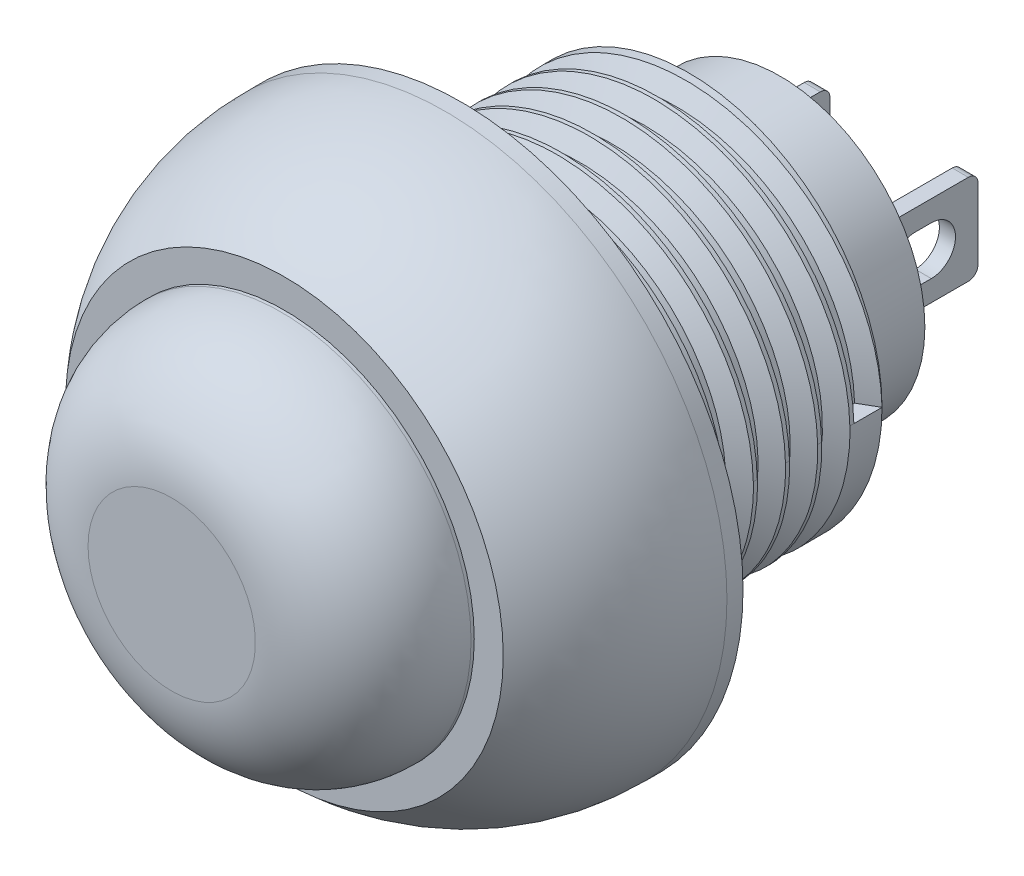
SolidWorks part; units mm, degrees
ref_plane "Front Plane" through (0, 0, 0) normal (0, 0, 1) x (1, 0, 0)
ref_plane "Top Plane" through (0, 0, 0) normal (0, 1, 0) x (1, 0, 0)
ref_plane "Right Plane" through (0, 0, 0) normal (1, 0, 0) x (0, 0, -1)
sketch "Sketch1" plane through (0, 0, 0) normal (0, 0, 1) x (1, 0, 0)
  circle A0 centre (0, 0) radius 6
  dimension "D1" = 12
extrude "Boss-Extrude1" add sketch "Sketch1" along normal blind 8.9
sketch "Sketch2" plane through (0, 0, 8.9) normal (0, 0, 1) x (1, 0, 0)
  circle A0 centre (0, 0) radius 6.8
  circle A1 centre (0, 0) radius 6 construction
  dimension "D1" = 0.8
extrude "Boss-Extrude2" add sketch "Sketch2" along normal blind 1
sketch "Sketch4" plane through (0, 0, 0) normal (0, 1, 0) x (1, 0, 0)
  line L0 (0, -9.9) -> (0, -16.6736) construction
  line L1 (-6.8, -9.9) -> (6.8, -9.9) construction
  line L2 (0, -9.9) -> (-8.75, -9.9)
  line L3 (-8.75, -9.9) -> (-8.75, -10.4)
  line L4 (-6.8, -15.4) -> (0, -15.4)
  line L5 (-6.8, -15.4) -> (-6.8, -20.524) construction
  line L6 (0, -15.4) -> (0, -9.9)
  arc A0 (-8.75, -10.4) -> (-6.8, -15.4) centre (-1.3647, -10.4) ccw
  dimension "D1" = 8.75
  dimension "D2" = 0.5
  dimension "D3" = 6.8
  dimension "D4" = 5.5
revolve "Revolve1" add sketch "Sketch4" angle 360 about L6
sketch "Sketch5" plane through (0, 0, 0) normal (0, 1, 0) x (1, 0, 0)
  line L1 (-6.8, -15.4) -> (6.8, -15.4) construction
  line L2 (-5.9, -15.4) -> (0, -15.4)
  line L4 (-5.9, -15.4) -> (-5.9, -15.5)
  line L5 (-2.6, -18.9) -> (0, -18.9)
  line L6 (0, -15.4) -> (0, -18.9)
  arc A0 (-5.9, -15.5) -> (-2.6, -18.9) centre (-2.4985, -15.5) ccw
  dimension "D1" = 3.5
  dimension "D3" = 0.1
  dimension "4" = 2.6
revolve "Revolve2" add sketch "Sketch5" angle 360 about L6
sketch "Sketch6" plane through (0, 0, 0) normal (0, 0, -1) x (-1, 0, 0)
  circle A0 centre (0, 0) radius 6
  circle A1 centre (0, 0) radius 4.5
  dimension "D1" = 9
extrude "Cut-Extrude1" cut sketch "Sketch6" against normal blind 2
chamfer "Chamfer1" distance 1.5 angle 29 1 edges at (-6, 0, 2) first distance on face at (-4.5, 0, 2)
sketch "Sketch7" plane through (0, 0, 0) normal (0, 0, -1) x (-1, 0, 0)
  line L1 (-2.55, 1.4) -> (-2.05, 1.4)
  line L2 (-2.55, 1.4) -> (-2.55, -1.4)
  line L3 (-2.55, -1.4) -> (-2.05, -1.4)
  line L4 (-2.05, 1.4) -> (-2.05, -1.4)
  line L5 (-2.3, 1.4) -> (-2.3, 2.5766) construction
  line L6 (2.05, 1.4) -> (2.55, 1.4)
  line L7 (2.05, 1.4) -> (2.05, -1.4)
  line L8 (2.05, -1.4) -> (2.55, -1.4)
  line L9 (2.55, 1.4) -> (2.55, -1.4)
  line L10 (2.3, 1.4) -> (2.3, 2.5766) construction
  point P7 (-2.05, 0)
  point P16 (2.05, 0)
  dimension "D1" = 0.5
  dimension "D2" = 0.5
  dimension "D3" = 4.6
  dimension "D4" = 2.05
  dimension "D5" = 2.8
extrude "Boss-Extrude3" add sketch "Sketch7" along normal blind 3.6
fillet "Fillet1" radius 0.3 4 edges at (2.3, -1.4, -3.6) (-2.3, -1.4, -3.6) (2.3, 1.4, -3.6) (-2.3, 1.4, -3.6)
sketch "Sketch8" plane through (2.55, 0, 0) normal (1, 0, 0) x (0, 0, -1)
  line L0 (3.6, 1.1) -> (3.6, -1.1) construction
  line L2 (1.65, 0) -> (2.15, 0) construction
  line L3 (1.65, 0.75) -> (2.15, 0.75)
  line L4 (1.65, -0.75) -> (2.15, -0.75)
  line L5 (0, 0) -> (3.6, 0) construction
  line L6 (0, -4.5) -> (0, 4.5) construction
  arc A0 (1.65, 0.75) -> (1.65, -0.75) centre (1.65, 0) ccw
  arc A1 (2.15, -0.75) -> (2.15, 0.75) centre (2.15, 0) ccw
  point P0 (2.9, 0)
  point P7 (1.9, 0)
  point P12 (0.9, 0)
  dimension "D1" = 2
  dimension "D2" = 0.7
  dimension "D3" = 1.5
extrude "Cut-Extrude2" cut sketch "Sketch8" against normal blind 6.6
thread "Thread1" pitch 1 method cut profile "Thread Profile1" start angle 0, offset 0, length 5, pitch 1, diameter 12
ref_plane "Plane1" through (6, 0, 2.8315) normal (0, -1, 0) x (1, 0, 0)
sketch "Thread Profile1" plane through (6, 0, 2.8315) normal (0, -1, 0) x (1, 0, 0)
  line L0 (0, 0) -> (0, 1) construction
  line L11 (0, 0) -> (0, 0.875)
  line L12 (0, 0.875) -> (-0.5413, 0.5625)
  line L13 (-0.5413, 0.5625) -> (-0.5413, 0.3125)
  line L15 (-0.5413, 0.3125) -> (0, 0)
  line L17 (-0.5413, 0.4375) -> (0, 0.4375) construction
  point P2 (0, 0)
  dimension "Pitch" = 1
  dimension "Profile_Angle" = 60
  dimension "Profile_Land" = 0.25
  dimension "Profile_Height" = 0.5413
